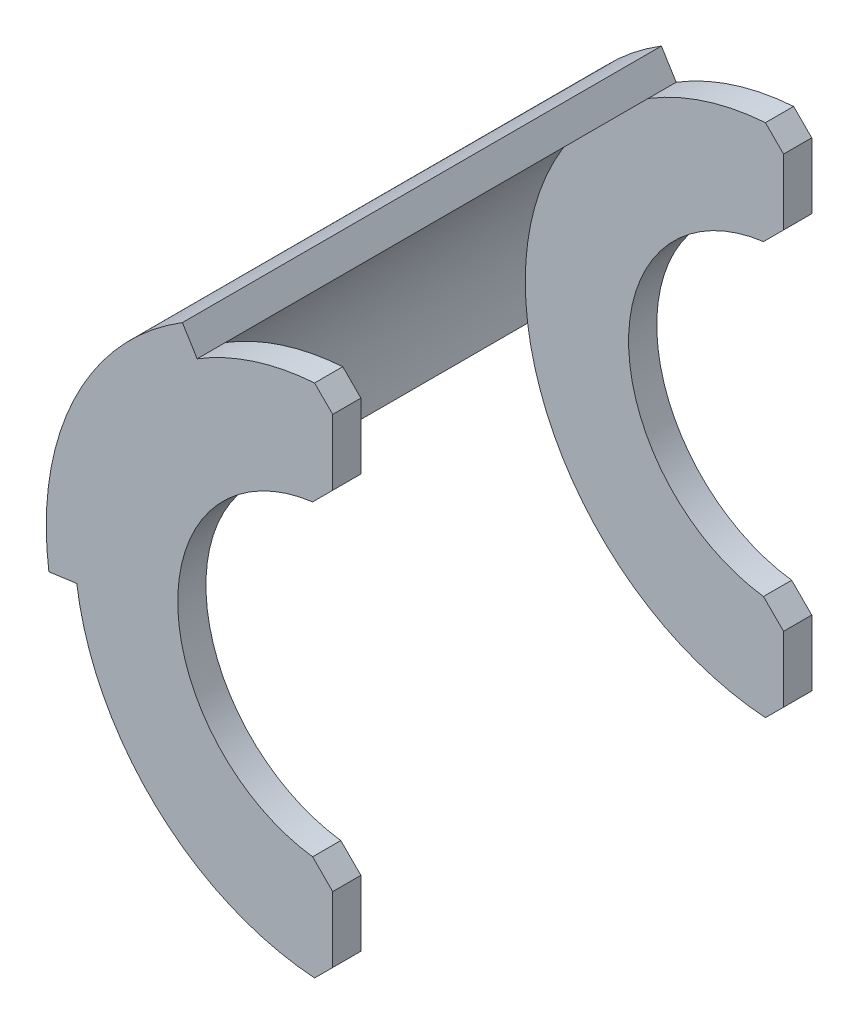
SolidWorks part; units mm, degrees
ref_plane "Front Plane" through (0, 0, 0) normal (0, 0, 1) x (1, 0, 0)
ref_plane "Top Plane" through (0, 0, 0) normal (0, 1, 0) x (1, 0, 0)
ref_plane "Right Plane" through (0, 0, 0) normal (1, 0, 0) x (0, 0, -1)
sketch "Sketch1" plane through (0, 0, 0) normal (0, 0, 1) x (1, 0, 0)
  line L0 (0, 27.5) -> (0, 16.5)
  line L1 (0, -16.5) -> (0, -27.5)
  arc A0 (0, 16.5) -> (0, -16.5) centre (0, 0) ccw
  arc A1 (0, 27.5) -> (0, -27.5) centre (0, 0) ccw
  dimension "D1" = 33
  dimension "D2" = 55
base flange "Base-Flange1" sketch "Sketch1" thickness 3 reverse thickness direction no parameters "D1"=0.7366
sketch "Sketch6" plane through (0, 0, 0) normal (0, 0, 1) x (1, 0, 0)
  line L0 (-14.4314, 23.4091) -> (-16.0057, 25.9628)
  line L1 (-27.2479, -3.7154) -> (-30.2204, -4.1207)
  arc A0 (-14.4314, 23.4091) -> (-27.2479, -3.7154) centre (0, 0) ccw
  arc A2 (-16.0057, 25.9628) -> (-30.2204, -4.1207) centre (0, 0) ccw
  circle A3 centre (0, 0) radius 27.5 construction
  circle A4 centre (0, 0) radius 30.5 construction
  dimension "D1" = 3
  dimension "D2" = 55
  dimension "D3" = 15
  dimension "D4" = 30
extrude "Boss-Extrude1" add sketch "Sketch6" against normal blind 51
sketch "Sketch7" plane through (0, 0, -51) normal (0, 0, -1) x (-1, 0, 0)
  line L0 (0, 27.5) -> (0, 16.5)
  line L1 (0, -16.5) -> (0, -27.5)
  arc A0 (0, -16.5) -> (0, 16.5) centre (0, 0) ccw
  arc A1 (0, -27.5) -> (0, 27.5) centre (0, 0) ccw
base flange "Base-Flange2" sketch "Sketch7" thickness 3 reverse thickness direction no parameters "D1"=0.7366
chamfer "Chamfer1" distance 2 angle 45 4 edges at (0, -27.5, -1.5) (0, -16.5, -1.5) (0, 16.5, -1.5) (0, 27.5, -1.5)
chamfer "Chamfer2" distance 2 angle 45 4 edges at (0, -27.5, -49.5) (0, -16.5, -49.5) (0, 16.5, -49.5) (0, 27.5, -49.5)
sketch "Bend-Lines1" [suppressed] plane through (0, 0, 0) normal (0, 1, 0) x (1, 0, 0)
sketch "Bounding-Box1" [suppressed] plane through (0, 0, 0) normal (0, 1, 0) x (1, 0, 0)
sheet metal parameters "Sheet-Metal1" thickness 3 parameters "D1"=0.7366
flat pattern "Flat-Pattern1" [suppressed]
sketch "Bend-Lines2" plane through (0, 0, 0) normal (0, 1, 0) x (1, 0, 0)
sketch3d "Bounding-Box2" [suppressed]
  line L0 (0, 27.5, 0) -> (0, -27.5, 0) construction
  line L1 (-27.5, 27.5, 0) -> (-27.5, -27.5, 0) construction
  line L2 (0, 27.5, 0) -> (-27.5, 27.5, 0) construction
  line L3 (0, -27.5, 0) -> (-27.5, -27.5, 0) construction
sheet metal parameters "Sheet-Metal2" thickness 3 parameters "D1"=0.7366
flat pattern "Flat-Pattern1"
sketch "Bend-Lines2" plane through (0, 0, 0) normal (0, 1, 0) x (1, 0, 0)
sketch3d "Bounding-Box2" [suppressed]
  line L0 (0, 27.432, 0) -> (0, -27.432, 0) construction
  line L1 (-30.5, 27.432, 0) -> (-30.5, -27.432, 0) construction
  line L2 (0, 27.432, 0) -> (-30.5, 27.432, 0) construction
  line L3 (0, -27.432, 0) -> (-30.5, -27.432, 0) construction
sheet metal parameters "Sheet-Metal3" thickness 3 parameters "D1"=0.7366
flat pattern "Flat-Pattern3"
sketch "Bend-Lines3" plane through (0, 0, 0) normal (0, 1, 0) x (1, 0, 0)
sketch3d "Bounding-Box3" [suppressed]
  line L0 (0, 27.432, 0) -> (0, -27.432, 0) construction
  line L1 (27.5, 27.432, 0) -> (27.5, -27.432, 0) construction
  line L2 (0, 27.432, 0) -> (27.5, 27.432, 0) construction
  line L3 (0, -27.432, 0) -> (27.5, -27.432, 0) construction
